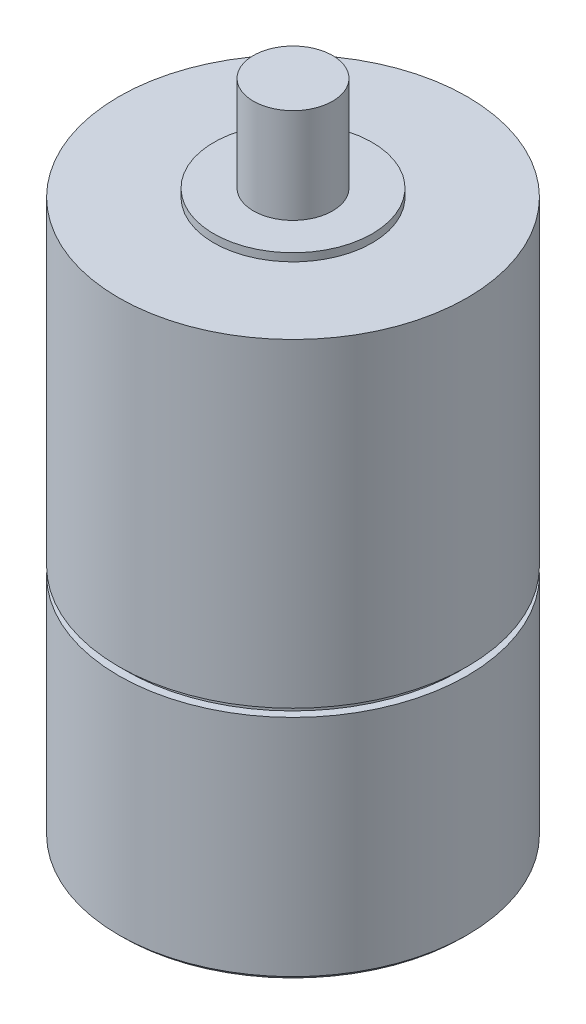
SolidWorks part; units mm, degrees
ref_plane "前视基准面" through (0, 0, 0) normal (0, 0, 1) x (1, 0, 0)
ref_plane "上视基准面" through (0, 0, 0) normal (0, 1, 0) x (1, 0, 0)
ref_plane "右视基准面" through (0, 0, 0) normal (1, 0, 0) x (0, 0, -1)
sketch "草图6" plane through (0, 0, 0) normal (0, 0, 1) x (1, 0, 0)
  line L0 (0, 0) -> (0, 98)
  line L1 (0, 98) -> (5, 98)
  line L2 (5, 98) -> (5, 73)
  line L3 (5, 73) -> (10, 73)
  line L4 (10, 73) -> (10, 72)
  line L5 (10, 72) -> (22, 72)
  line L6 (22, 72) -> (22, 31.6815)
  line L7 (22, 31.6815) -> (21, 31.6815)
  line L8 (21, 31.6815) -> (21, 30.6815)
  line L9 (21, 30.6815) -> (22, 30.6815)
  line L10 (22, 30.6815) -> (22, 2.338)
  line L11 (22, 2.338) -> (21.5, 1.838)
  line L12 (21.5, 1.838) -> (5, 1.838)
  line L13 (5, 1.838) -> (5, 0)
  line L14 (5, 0) -> (0, 0)
  dimension "D1" = 98
  dimension "D2" = 5
  dimension "D3" = 25
  dimension "D4" = 5
  dimension "D5" = 1
  dimension "D6" = 12
  dimension "D7" = 1
  dimension "D8" = 1
  dimension "D9" = 16.5
ref_plane "基准面1" through (0, 20, 0) normal (0, 1, 0) x (1, 0, 0)
sketch "草图7" plane through (0, 20, 0) normal (0, 1, 0) x (1, 0, 0)
  circle A0 centre (0, 0) radius 8.2222
sweep "扫描1" add profiles "草图6" path "草图7"
sketch "草图8" plane through (0, 0, 0) normal (0, 0, 1) x (1, 0, 0)
  circle A0 centre (0, 90.2226) radius 1.5
  dimension "D1" = 3
extrude "切除-拉伸1" cut sketch "草图8" against normal blind 3 and the other way blind 23 contours A0
thread "螺纹线2" pitch 0.3175 method extrude profile "螺纹线轮廓3" start angle 0, offset 0, length 7.5, pitch 0.3175, diameter 3
ref_plane "基准面4" through (1.5, 90.2226, -3) normal (0, -1, 0) x (1, 0, 0)
sketch "螺纹线轮廓3" plane through (1.5, 90.2226, -3) normal (0, -1, 0) x (1, 0, 0)
  line L0 (0, 0) -> (0, 0.3175) construction
  line L11 (0, 0) -> (0, 0.2778)
  line L12 (0, 0.2778) -> (-0.1719, 0.1786)
  line L13 (-0.1719, 0.1786) -> (-0.1719, 0.0992)
  line L15 (-0.1719, 0.0992) -> (0, 0)
  line L17 (-0.1719, 0.1389) -> (0, 0.1389) construction
  point P2 (0, 0)
  dimension "Pitch" = 0.3175
  dimension "Profile_Angle" = 60
  dimension "Profile_Land" = 0.0794
  dimension "Profile_Height" = 0.1719
ref_plane "基准面5" through (0, 100, 0) normal (0, 1, 0) x (1, 0, 0)
sketch "草图9" plane through (0, 100, 0) normal (0, 1, 0) x (1, 0, 0)
  circle A0 centre (0, 0) radius 5
extrude "切除-拉伸2" cut sketch "草图9" against normal blind 15
